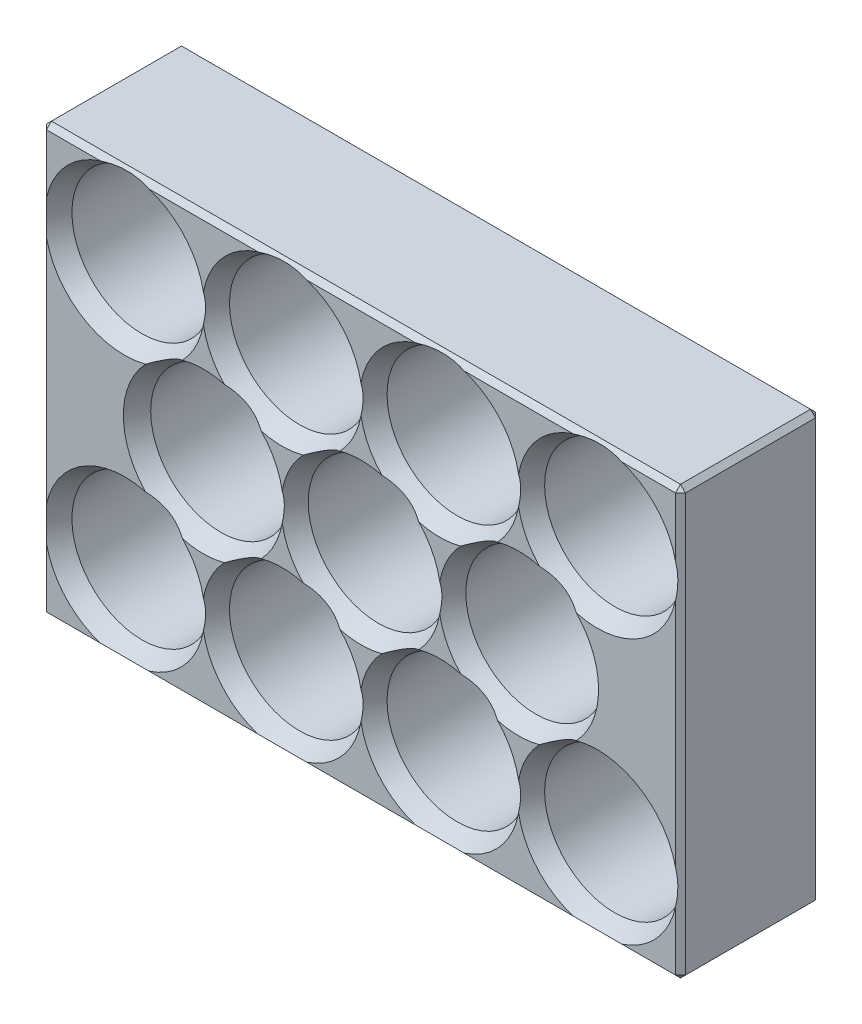
SolidWorks part; units mm, degrees
ref_plane "Plan de face" through (0, 0, 0) normal (0, 0, 1) x (1, 0, 0)
ref_plane "Plan de dessus" through (0, 0, 0) normal (0, 1, 0) x (1, 0, 0)
ref_plane "Plan de droite" through (0, 0, 0) normal (1, 0, 0) x (0, 0, -1)
sketch "Esquisse1" plane through (0, 0, 0) normal (0, 0, 1) x (1, 0, 0)
  line L1 (0, 0) -> (127.76, 0)
  line L2 (0, 0) -> (0, 85.48)
  line L3 (0, 85.48) -> (127.76, 85.48)
  line L4 (127.76, 0) -> (127.76, 85.48)
  dimension "D1" = 85.48
  dimension "D2" = 127.76
extrude "Boss.-Extru.1" add sketch "Esquisse1" along normal blind 28
sketch "Esquisse2" plane through (0, 0, 28) normal (0, 0, 1) x (1, 0, 0)
  line L0 (16.63, 69.24) -> (16.63, 16.24) construction
  line L1 (95.38, 42.74) -> (32.38, 42.74) construction
  line L2 (16.63, 69.24) -> (111.13, 69.24)
  line L3 (0, 85.48) -> (0, 0) construction
  line L4 (127.76, 85.48) -> (0, 85.48) construction
  circle A0 centre (16.63, 69.24) radius 14
  circle A1 centre (48.13, 69.24) radius 14
  circle A2 centre (79.63, 69.24) radius 14
  circle A3 centre (111.13, 69.24) radius 14
  circle A4 centre (32.38, 42.74) radius 14
  circle A5 centre (16.63, 16.24) radius 14
  circle A8 centre (48.13, 16.24) radius 14
  circle A9 centre (111.13, 16.24) radius 14
  circle A10 centre (79.63, 16.24) radius 14
  circle A11 centre (63.88, 42.74) radius 14
  circle A12 centre (95.38, 42.74) radius 14
  point P12 (16.63, 42.74)
  point P13 (63.88, 69.24)
  point P30 (0, 42.74)
  point P34 (63.88, 85.48)
  dimension "D1" = 28
  dimension "D4" = 31.5
  dimension "D5" = 31.5
  dimension "D6" = 53
  dimension "D2" = 4
  dimension "D3" = 3
extrude "Enlèv. mat.-Extru.1" cut sketch "Esquisse2" against normal blind 25 contours A8 | A5 | A4 | A0 | L2 A1 | L2 A1 | L2 A2 | L2 A2 | A3 | A11 | A12 | A10 | A9 region at (111.13, 82.844, 28) region at (79.63, 75.1818, 28) region at (79.63, 63.2982, 28) region at (48.13, 75.1818, 28) region at (48.13, 63.2982, 28) region at (3.026, 69.24, 28) region at (32.38, 42.74, 28) region at (16.63, 16.24, 28) region at (48.13, 16.24, 28) region at (111.13, 16.24, 28) region at (79.63, 16.24, 28) region at (63.88, 42.74, 28) region at (95.38, 42.74, 28)
chamfer "Chanfrein1" distance 2 angle 60 11 edges at (30.63, 16.24, 28) (46.38, 42.74, 28) (62.13, 16.24, 28) (77.88, 42.74, 28) (93.63, 16.24, 28) (125.13, 16.24, 28) (109.38, 42.74, 28) (125.13, 69.24, 28) (93.63, 69.24, 28) (62.13, 69.24, 28) (30.63, 69.24, 28) first distance on face at (93.63, 69.24, 28)
chamfer "Chanfrein2" distance 1 angle 45 12 edges at (63.88, 85.48, 28) (63.88, 85.48, 0) (127.76, 42.74, 28) (127.76, 85.48, 14) (127.76, 42.74, 0) (63.88, 0, 28) (127.76, 0, 14) (63.88, 0, 0) (0, 85.48, 14) (0, 42.74, 28) (0, 0, 14) (0, 42.74, 0)
